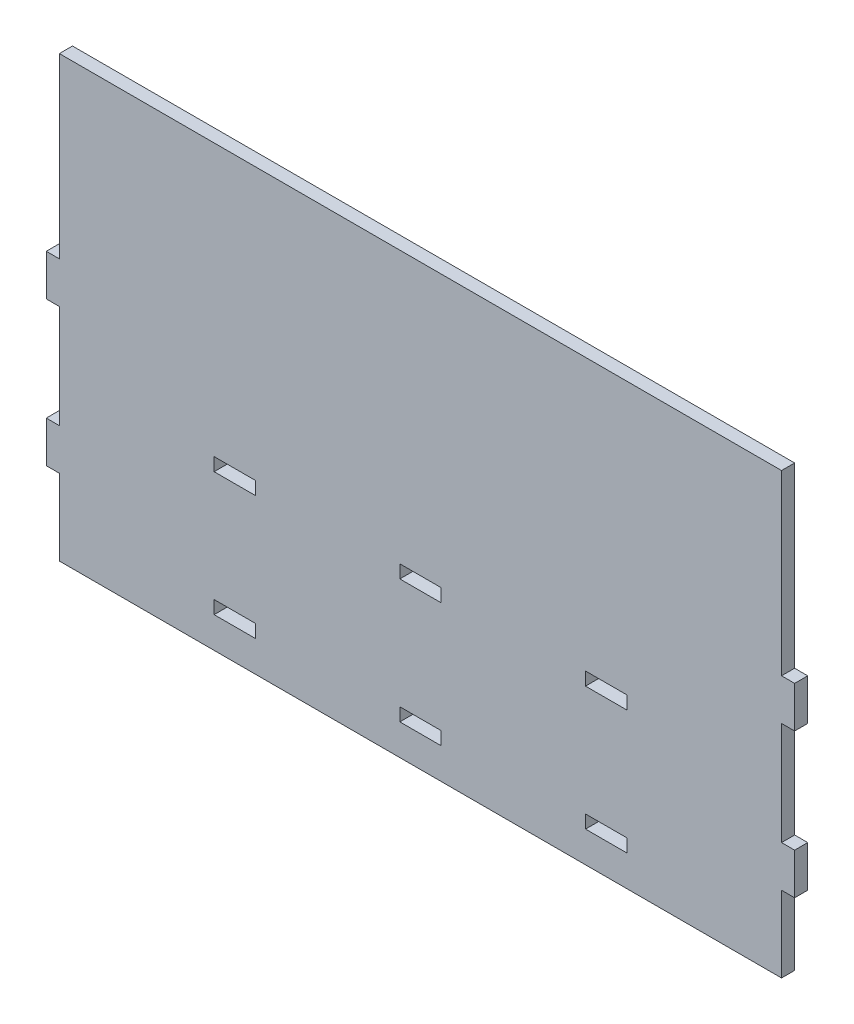
SolidWorks part; units mm, degrees
ref_plane "Alzado" through (0, 0, 0) normal (0, 0, 1) x (1, 0, 0)
ref_plane "Planta" through (0, 0, 0) normal (0, 1, 0) x (1, 0, 0)
ref_plane "Vista lateral" through (0, 0, 0) normal (1, 0, 0) x (0, 0, -1)
sketch "Croquis1" plane through (0, 0, 0) normal (0, 0, 1) x (1, 0, 0)
  line L1 (-150, 3.4711) -> (200, 3.4711)
  line L2 (-150, 3.4711) -> (-150, 201.4711)
  line L3 (-150, 201.4711) -> (200, 201.4711)
  line L4 (200, 3.4711) -> (200, 201.4711)
  dimension "D1" = 350
  dimension "D2" = 198
extrude "Saliente-Extruir1" add sketch "Croquis1" along normal blind 6.35
sketch "Croquis2" plane through (-150, 0, 0) normal (-1, 0, 0) x (0, 0, 1)
  line L0 (0, 201.4711) -> (0, 3.4711) construction
  line L1 (0, 45.3111) -> (6.35, 45.3111)
  line L2 (0, 45.3111) -> (0, 25.3111)
  line L3 (0, 25.3111) -> (6.35, 25.3111)
  line L4 (6.35, 45.3111) -> (6.35, 25.3111)
  line L5 (6.35, 201.4711) -> (6.35, 3.4711) construction
  line L6 (6.35, 3.4711) -> (0, 3.4711) construction
  line L8 (6.35, 95.3111) -> (0, 95.3111)
  line L9 (6.35, 95.3111) -> (6.35, 115.3111)
  line L10 (6.35, 115.3111) -> (0, 115.3111)
  line L11 (0, 95.3111) -> (0, 115.3111)
  dimension "D1" = 21.84
  dimension "D2" = 20
  dimension "D3" = 20
  dimension "D4" = 50
extrude "Saliente-Extruir2" add sketch "Croquis2" along normal blind 6.35
ref_plane "Plano1" through (25, 0, 0) normal (1, 0, 0) x (0, 0, -1)
mirror "Simetría1" about plane through (25, 0, 0) normal (1, 0, 0) of "Saliente-Extruir2"
sketch "Croquis3" plane through (0, 0, 0) normal (0, 0, -1) x (-1, 0, 0)
  line L0 (150, 3.4711) -> (-200, 3.4711) construction
  line L1 (-35, 3.4711) -> (-15, 3.4711)
  line L2 (-35, 3.4711) -> (-35, 9.8211)
  line L3 (-35, 9.8211) -> (-15, 9.8211)
  line L4 (-15, 3.4711) -> (-15, 9.8211)
  line L25 (55, 3.4711) -> (75, 3.4711)
  line L26 (55, 3.4711) -> (55, 9.8211)
  line L27 (55, 9.8211) -> (75, 9.8211)
  line L28 (75, 3.4711) -> (75, 9.8211)
  line L29 (-125, 3.4711) -> (-105, 3.4711)
  line L30 (-125, 3.4711) -> (-125, 9.8211)
  line L31 (-125, 9.8211) -> (-105, 9.8211)
  line L32 (-105, 3.4711) -> (-105, 9.8211)
  line L33 (-35, 63.4711) -> (-15, 63.4711)
  line L34 (-35, 63.4711) -> (-35, 69.8211)
  line L35 (-35, 69.8211) -> (-15, 69.8211)
  line L36 (-15, 63.4711) -> (-15, 69.8211)
  line L37 (55, 63.4711) -> (75, 63.4711)
  line L38 (55, 63.4711) -> (55, 69.8211)
  line L39 (55, 69.8211) -> (75, 69.8211)
  line L40 (75, 63.4711) -> (75, 69.8211)
  line L41 (-125, 63.4711) -> (-105, 63.4711)
  line L42 (-125, 63.4711) -> (-125, 69.8211)
  line L43 (-125, 69.8211) -> (-105, 69.8211)
  line L44 (-105, 63.4711) -> (-105, 69.8211)
  point P6 (-25, 3.4711)
  point P7 (-25, 9.8211)
  dimension "D1" = 6.35
  dimension "D2" = 20
extrude "Cortar-Extruir1" cut sketch "Croquis3" against normal blind 6.35
sketch "Croquis4" plane through (0, 0, 6.35) normal (0, 0, 1) x (1, 0, 0)
  line L0 (200, 3.4711) -> (200, 25.3111) construction
  line L1 (-150, 3.4711) -> (200, 3.4711)
  line L2 (-150, 3.4711) -> (-150, -11.5289)
  line L3 (-150, -11.5289) -> (200, -11.5289)
  line L4 (200, 3.4711) -> (200, -11.5289)
  dimension "D1" = 15
extrude "Saliente-Extruir3" add sketch "Croquis4" against normal up to surface (6.35 mm away) up to face at (25, 50.4567, 0)
